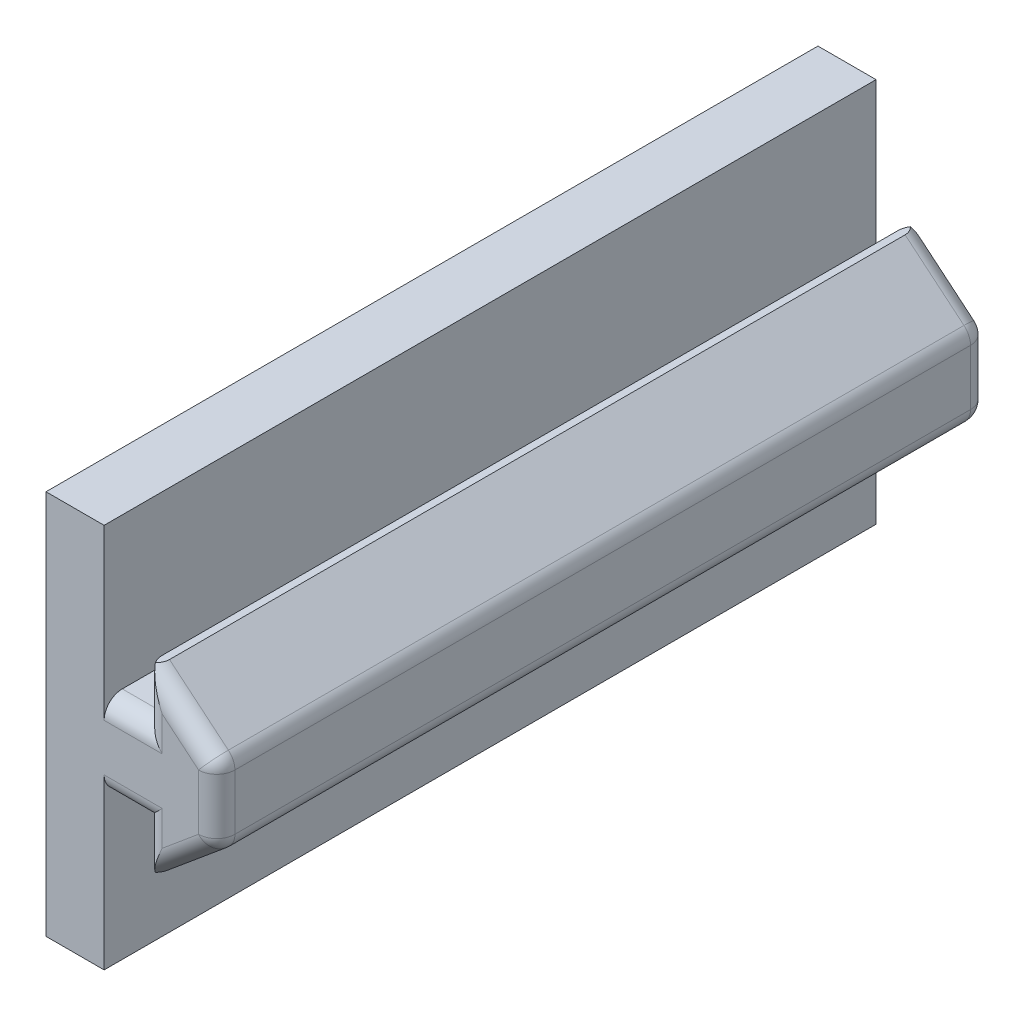
SolidWorks part; units mm, degrees
ref_plane "Front Plane" through (0, 0, 0) normal (0, 0, 1) x (1, 0, 0)
ref_plane "Top Plane" through (0, 0, 0) normal (0, 1, 0) x (1, 0, 0)
ref_plane "Right Plane" through (0, 0, 0) normal (1, 0, 0) x (0, 0, -1)
ref_plane "Plane1" through (0, 0, 26.9875) normal (0, 0, 1) x (1, 0, 0)
sketch "Sketch1" plane through (0, 0, 26.9875) normal (0, 0, 1) x (1, 0, 0)
  line L0 (3.302, 6.35) -> (-4.064, 6.35)
  line L1 (-4.064, 6.35) -> (-4.064, -6.35)
  line L2 (-4.064, -6.35) -> (3.302, -6.35)
  line L3 (3.302, -6.35) -> (7.874, -2.54)
  line L4 (7.874, -2.54) -> (7.874, 2.54)
  line L5 (7.874, 2.54) -> (3.302, 6.35)
extrude "Boss-Extrude1" add sketch "Sketch1" against normal blind 53.975
sketch "Sketch2" plane through (0, 0, 26.9875) normal (0, 0, 1) x (1, 0, 0)
  line L0 (-4.064, 6.35) -> (-4.064, 2.921)
  line L1 (-4.064, 2.921) -> (2.794, 2.921)
  line L2 (2.794, 2.921) -> (2.794, 6.35)
  line L3 (2.794, 6.35) -> (-4.064, 6.35)
extrude "Cut-Extrude1" cut sketch "Sketch2" against normal through all
sketch "Sketch15" [suppressed] plane through (-4.064, 0, 0) normal (-1, 0, 0) x (0, 0, 1)
  line L0 (-30.2895, -6.35) -> (23.6855, -6.35) construction
  line L1 (23.6855, 7.112) -> (-30.2895, 7.112)
  line L2 (23.6855, 7.112) -> (23.6855, -19.812)
  line L3 (23.6855, -19.812) -> (-30.2895, -19.812)
  line L4 (-30.2895, 7.112) -> (-30.2895, -19.812)
  line L5 (23.6855, 7.112) -> (-30.2895, -19.812) construction
  line L6 (23.6855, -19.812) -> (-30.2895, 7.112) construction
  point P0 (-3.302, -6.35)
  point P5 (-3.8596, -2.1834)
  point P6 (-3.3595, -0.9899)
  point P7 (-2.5182, -0.9448)
  point P8 (0, -1.7145)
  point P9 (-3.302, -6.35)
  point P12 (-3.302, -6.35)
  point P13 (-3.302, -6.35)
  point P14 (-3.302, -6.35)
  point P15 (-3.302, -6.35)
  point P16 (-3.302, -6.35)
  point P17 (-3.302, -6.35)
  dimension "D1" = 26.924
sketch "Sketch3" [suppressed] plane through (0, 2.921, 0) normal (0, 1, 0) x (-1, 0, 0)
  line L0 (4.064, -30.1669) -> (0, -30.1669)
  line L1 (0, -30.1669) -> (0, 23.8081)
  line L2 (0, 23.8081) -> (4.064, 23.8081)
  line L3 (4.064, 23.8081) -> (4.064, -30.1669)
  dimension "D1" = 53.975
extrude "Boss-Extrude2" [suppressed] add sketch "Sketch3" along normal blind 7.366
sketch "Sketch4" plane through (0, 0, 26.9875) normal (0, 0, 1) x (1, 0, 0)
  line L0 (-4.064, -6.35) -> (2.794, -6.35)
  line L1 (2.794, -6.35) -> (2.794, -2.921)
  line L2 (2.794, -2.921) -> (-4.064, -2.921)
  line L3 (-4.064, -2.921) -> (-4.064, -6.35)
extrude "Cut-Extrude2" cut sketch "Sketch4" against normal through all
sketch "Sketch5" [suppressed] plane through (0, -2.921, 0) normal (0, -1, 0) x (1, 0, 0)
  line L0 (0, -33.4644) -> (-4.064, -33.4644)
  line L1 (-4.064, -33.4644) -> (-4.064, 20.5106)
  line L2 (-4.064, 20.5106) -> (0, 20.5106)
  line L3 (0, 20.5106) -> (0, -33.4644)
  dimension "D1" = 53.975
extrude "Boss-Extrude3" [suppressed] add sketch "Sketch5" along normal blind 7.366
sketch "Sketch18" plane through (-4.064, 0, 0) normal (-1, 0, 0) x (0, 0, 1)
  line L1 (-26.9875, -13.462) -> (26.9875, -13.462)
  line L2 (-26.9875, -13.462) -> (-26.9875, 13.462)
  line L3 (-26.9875, 13.462) -> (26.9875, 13.462)
  line L4 (26.9875, -13.462) -> (26.9875, 13.462)
  line L5 (-26.9875, -13.462) -> (26.9875, 13.462) construction
  line L6 (-26.9875, 13.462) -> (26.9875, -13.462) construction
  point P0 (0, 0)
  dimension "D1" = 26.924
extrude "Boss-Extrude5" add sketch "Sketch18" against normal blind 4.064
extrude "Boss-Extrude4" [suppressed] add sketch "Sketch15" against normal blind 4.064
hole_wizard "#3 Clearance Hole1" [suppressed] positions "Sketch7" profile "Sketch6" hole size "#3" standard "ANSI Inch"
sketch "Sketch7" plane through (-4.064, 0, 0) normal (-1, 0, 0) x (0, 0, 1)
  point P0 (12.7, 0)
  point P1 (-12.7, 0)
sketch "Sketch6" plane through (-4.064, 0, 12.7) normal (0, 1, 0) x (0, 0, 1)
  line L0 (0, 0) -> (0, 11.938)
  line L1 (0, 11.938) -> (1.3843, 11.938)
  line L2 (1.3843, 11.938) -> (1.3843, 0)
  line L5 (1.3843, 0) -> (0, 0)
  line L11 (0, -6.35) -> (0, 107.95) construction
  dimension "Thru Hole Dia." = 2.7686
  dimension "Thru Hole Depth" = 11.938
sketch "Sketch12" [suppressed] plane through (7.874, 0, 0) normal (1, 0, 0) x (0, 0, -1)
  line L0 (-12.7, 1.3843) -> (-12.7, -1.3843) construction
  line L1 (12.7, 1.3843) -> (12.7, -1.3843) construction
  circle A0 centre (-12.7, 0) radius 1.3843 construction
  circle A1 centre (12.7, 0) radius 1.3843 construction
  point P5 (-12.7, 0)
  point P11 (12.7, 0)
hole_wizard "CBORE for #10 Button Head Cap Screw1" [suppressed] positions "Sketch13" profile "Sketch14" counterbore size "#10" standard "ANSI Inch"
sketch "Sketch13" [suppressed] plane through (7.874, 0, 0) normal (1, 0, 0) x (0, 0, -1)
  point P0 (-12.7, 0)
  point P3 (12.7, 0)
sketch "Sketch14" plane through (7.874, 0, 12.7) normal (0, 1, 0) x (0, 0, -1)
  line L0 (0, 0) -> (0, 13.4708)
  line L1 (0, 13.4708) -> (2.5527, 11.937)
  line L2 (2.5527, 11.937) -> (2.5527, 3.2004)
  line L3 (2.5527, 3.2004) -> (4.9606, 3.2004)
  line L4 (4.9606, 3.2004) -> (4.9606, 0)
  line L5 (4.9606, 0) -> (0, 0)
  line L10 (0, 13.4708) -> (-2.5527, 11.937) construction
  line L11 (0, -6.35) -> (0, 107.95) construction
  dimension "Hole Dia." = 5.1054
  dimension "Hole Depth" = 11.937
  dimension "C'Bore Dia." = 9.9212
  dimension "C'Bore Depth" = 3.2004
  dimension "Drill Angle" = 118
fillet "Fillet1" radius 1.27 2 edges at (7.874, -2.54, 0) (7.874, 2.54, 0)
fillet "Fillet3" radius 1.27 9 edges at (5.3595, -4.6354, -26.9875) (7.7541, -2.4838, -26.9875) (5.3595, 4.6354, -26.9875) (7.7541, 2.4838, -26.9875) (1.397, -2.921, -26.9875) (1.397, 2.921, -26.9875) (2.794, 4.6355, -26.9875) (2.794, -4.6355, -26.9875) (7.874, 0, -26.9875)
fillet "Fillet5" radius 1.27 9 edges at (5.3595, -4.6354, 26.9875) (7.7541, -2.4838, 26.9875) (5.3595, 4.6354, 26.9875) (7.7541, 2.4838, 26.9875) (2.794, 4.6355, 26.9875) (1.397, 2.921, 26.9875) (1.397, -2.921, 26.9875) (2.794, -4.6355, 26.9875) (7.874, 0, 26.9875)
